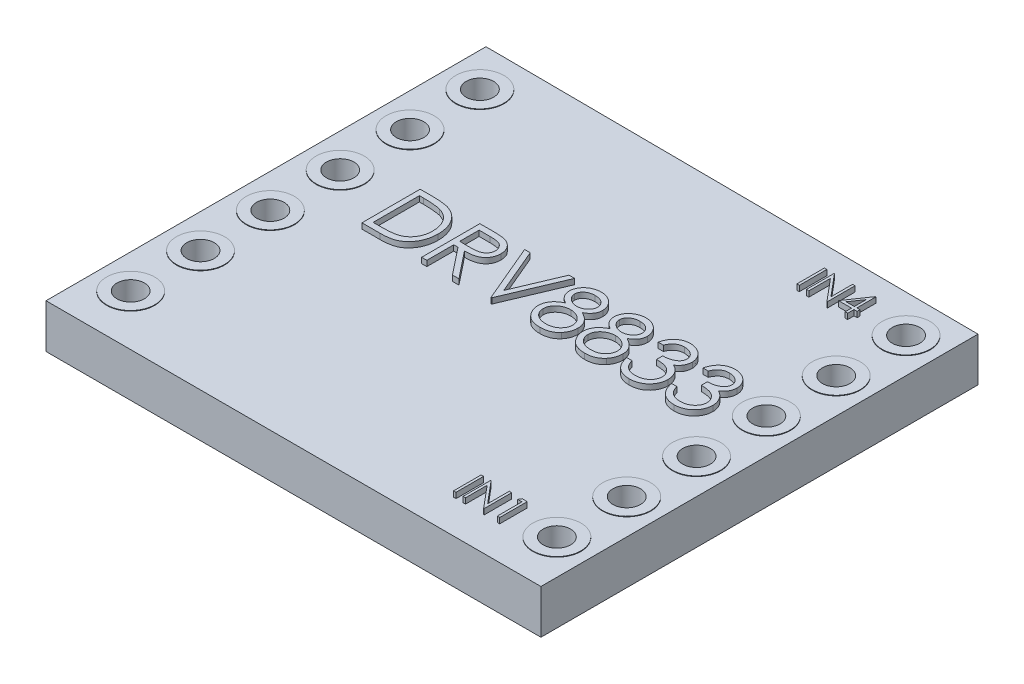
SolidWorks part; units mm, degrees
ref_plane "Front Plane" through (0, 0, 0) normal (0, 0, 1) x (1, 0, 0)
ref_plane "Top Plane" through (0, 0, 0) normal (0, 1, 0) x (1, 0, 0)
ref_plane "Right Plane" through (0, 0, 0) normal (1, 0, 0) x (0, 0, -1)
sketch "Sketch2" plane through (0, 0, 0) normal (0, 1, 0) x (1, 0, 0)
  line L0 (41.4855, 331.984) -> (59.4852, 331.8769) construction
  line L2 (41.4784, 331.9811) -> (59.4784, 331.9811)
  line L3 (41.4784, 331.9811) -> (41.4784, 315.9811)
  line L4 (41.4784, 315.9811) -> (59.4784, 315.9811)
  line L5 (59.4784, 331.9811) -> (59.4784, 315.9811)
  circle A0 centre (42.7284, 330.5104) radius 0.5
  circle A1 centre (42.7284, 330.5104) radius 0.875
  circle A3 centre (58.2284, 330.5104) radius 0.5
  circle A4 centre (58.2284, 330.5104) radius 0.875
  circle A5 centre (58.2284, 327.9704) radius 0.5
  circle A6 centre (58.2284, 327.9704) radius 0.875
  circle A7 centre (58.2284, 325.4304) radius 0.5
  circle A8 centre (58.2284, 325.4304) radius 0.875
  circle A9 centre (58.2284, 322.8904) radius 0.5
  circle A10 centre (58.2284, 322.8904) radius 0.875
  circle A11 centre (58.2284, 320.3504) radius 0.5
  circle A12 centre (58.2284, 320.3504) radius 0.875
  circle A13 centre (58.2284, 317.8104) radius 0.5
  circle A14 centre (58.2284, 317.8104) radius 0.875
  circle A15 centre (42.7284, 327.9704) radius 0.5
  circle A16 centre (42.7284, 327.9704) radius 0.875
  circle A17 centre (42.7284, 325.4304) radius 0.5
  circle A18 centre (42.7284, 325.4304) radius 0.875
  circle A19 centre (42.7284, 322.8904) radius 0.5
  circle A20 centre (42.7284, 322.8904) radius 0.875
  circle A21 centre (42.7284, 320.3504) radius 0.5
  circle A22 centre (42.7284, 320.3504) radius 0.875
  circle A23 centre (42.7284, 317.8104) radius 0.5
  circle A24 centre (42.7284, 317.8104) radius 0.875
  dimension "D5" = 1
  dimension "D6" = 1.75
  dimension "D7" = 2
  dimension "D1" = 18
  dimension "D2" = 18
  dimension "D3" = 16
  dimension "D4" = 1.25
  dimension "D8" = 6
extrude "Boss-Extrude1" add sketch "Sketch2" along normal blind 1.6 contours L0 L2 L3 L4 L5 A24 A22 A20 A18 A16 A14 A12 A10 A8 A6 A4 A1 region at (50.4672, 0, -323.9329)
extrude "Boss-Extrude2" add sketch "Sketch2<4>" along normal blind 1.62 contours A1 A0 | A16 A15 | A18 A17 | A20 A19 | A22 A21 | A24 A23 | A14 A13 | A12 A11 | A10 A9 | A8 A7 | A6 A5 | A4 A3 region at (41.8781, 0, -330.5104) region at (57.3781, 0, -330.5104) region at (57.3781, 0, -327.9704) region at (57.3781, 0, -325.4304) region at (57.3781, 0, -322.8904) region at (57.3781, 0, -320.3504) region at (57.3781, 0, -317.8104) region at (41.8781, 0, -327.9704) region at (41.8781, 0, -325.4304) region at (41.8781, 0, -322.8904) region at (41.8781, 0, -320.3504) region at (41.8781, 0, -317.8104)
sketch "Sketch2<4>" plane through (0, 0, 0) normal (0, 1, 0) x (1, 0, 0) same geometry as "Sketch2"
sketch "Sketch3" plane through (0, 1.6, 0) normal (0, 1, 0) x (1, 0, 0)
  text T0 "DRV8833" font "Century Gothic" height in points 8
  text T1 "IN4" font "Century Gothic" height 1
  text T2 "IN1" font "Century Gothic" height 1
  point P3 (44.6979, 295.978)
  point P4 (59.1284, 295.978)
extrude "Boss-Extrude3" add sketch "Sketch3" along normal blind 0.2
